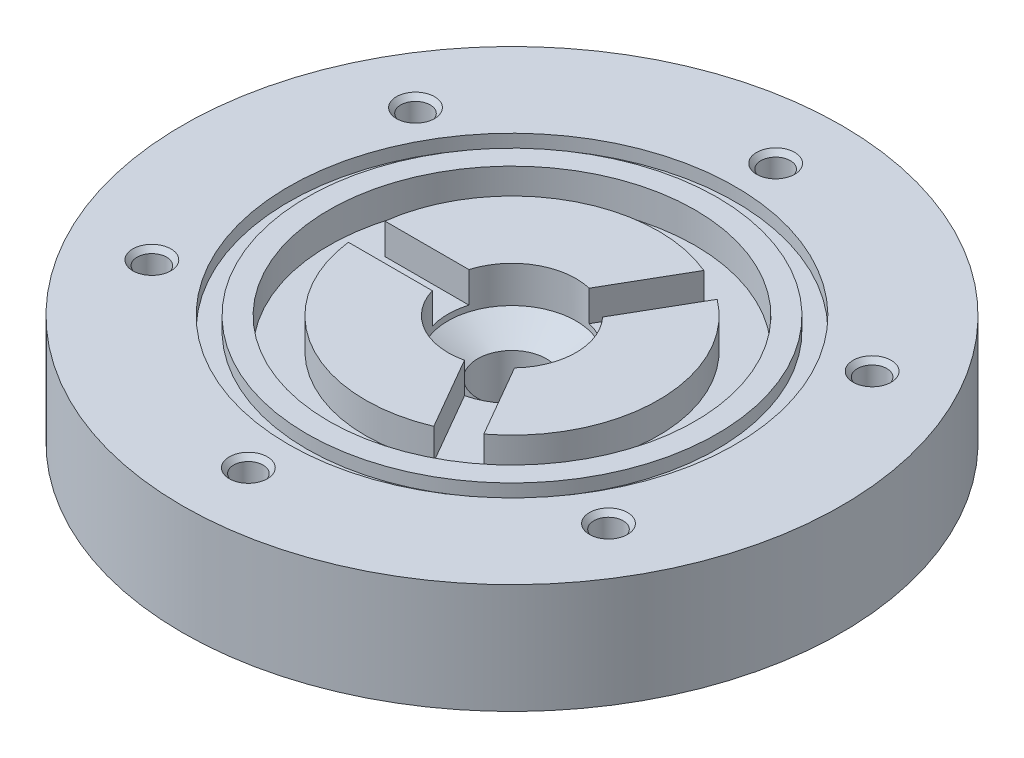
SolidWorks part; units mm, degrees
ref_plane "Front Plane" through (0, 0, 0) normal (0, 0, 1) x (1, 0, 0)
ref_plane "Top Plane" through (0, 0, 0) normal (0, 1, 0) x (1, 0, 0)
ref_plane "Right Plane" through (0, 0, 0) normal (1, 0, 0) x (0, 0, -1)
sketch "Sketch1" plane through (0, 0, 0) normal (0, 1, 0) x (1, 0, 0)
  circle A0 centre (0, 0) radius 57.15
  point P0 (0, 0)
  dimension "D3" = 114.3
extrude "Boss-Extrude1" add sketch "Sketch1" along normal blind 19.05
hole_wizard "7/8 (0.875) Diameter Hole1" positions "Sketch2" profile "Sketch3" hole size "7/8" standard "ANSI Inch"
sketch "Sketch2" plane through (0, 19.05, 0) normal (0, 1, 0) x (1, 0, 0)
  point P0 (0, 0)
sketch "Sketch3" plane through (0, 19.05, 0) normal (1, 0, 0) x (0, 0, 1)
  line L0 (0, 0) -> (0, 13.0271)
  line L1 (0, 13.0271) -> (11.1125, 6.35)
  line L2 (11.1125, 6.35) -> (11.1125, 0)
  line L5 (11.1125, 0) -> (0, 0)
  line L10 (0, 13.0271) -> (-11.1125, 6.35) construction
  line L11 (0, -6.35) -> (0, 107.95) construction
  dimension "Hole Dia." = 22.225
  dimension "Hole Depth" = 6.35
  dimension "Drill Angle" = 118
sketch "Sketch4" plane through (0, 19.05, 0) normal (0, 1, 0) x (1, 0, 0)
  circle A0 centre (0, 0) radius 5.9531
  dimension "D1" = 11.9062
extrude "Cut-Extrude1" cut sketch "Sketch4" against normal through all both and the other way through all
sketch "Sketch5" plane through (0, 19.05, 0) normal (0, 1, 0) x (1, 0, 0)
  line L0 (0, 0) -> (-57.15, 0) construction
  line L2 (-10.6493, 3.175) -> (-25.2008, 3.175)
  line L3 (-10.6493, -3.175) -> (-25.2008, -3.175)
  line L4 (0, -3.175) -> (-63.5, -3.175) construction
  line L5 (0, 3.175) -> (-63.5, 3.175) construction
  line L6 (2.575, 10.81) -> (9.8508, 23.412)
  line L7 (8.0743, 7.635) -> (15.35, 20.237)
  line L8 (0, 0) -> (28.575, 49.4934) construction
  line L9 (8.0743, -7.635) -> (15.35, -20.237)
  line L10 (2.575, -10.81) -> (9.8508, -23.412)
  line L11 (0, 0) -> (28.575, -49.4934) construction
  line L12 (0, 0) -> (-63.5, 0) construction
  arc A0 (15.35, -20.237) -> (15.35, 20.237) centre (0, 0) ccw
  circle A1 centre (0, 0) radius 31.75
  arc A2 (2.575, -10.81) -> (8.0743, -7.635) centre (0, 0) ccw
  arc A3 (-10.6493, 3.175) -> (-10.6493, -3.175) centre (0, 0) ccw
  arc A4 (8.0743, 7.635) -> (2.575, 10.81) centre (0, 0) ccw
  arc A5 (-25.2008, -3.175) -> (9.8508, -23.412) centre (0, 0) ccw
  arc A6 (9.8508, 23.412) -> (-25.2008, 3.175) centre (0, 0) ccw
  circle A8 centre (0, 0) radius 57.15 construction
  point P29 (0, 0)
  dimension "D1" = 50.8
  dimension "D2" = 63.5
  dimension "D5" = 22.225
  dimension "D3" = 3.175
  dimension "D4" = 3.175
  dimension "D6" = 3
ref_axis "Axis1" through (0, 12.7, 0) along (0, 1, 0)
extrude "Cut-Extrude3" cut sketch "Sketch5" against normal blind 5.334
sketch "Sketch6" plane through (0, 19.05, 0) normal (0, 1, 0) x (1, 0, 0)
  circle A0 centre (0, 0) radius 53.975 construction
  dimension "D1" = 107.95
sketch "Sketch7" plane through (0, 19.05, 0) normal (0, 1, 0) x (1, 0, 0)
  circle A0 centre (0, 0) radius 35.56
  circle A1 centre (0, 0) radius 38.735
  dimension "D1" = 71.12
  dimension "D2" = 77.47
extrude "Cut-Extrude5" cut sketch "Sketch7" against normal blind 2.286
hole_wizard "1/4-20 Tapped Hole1" positions "Sketch8" profile "Sketch9" tap size "1/4-20" standard "ANSI Inch"
sketch "Sketch8" plane through (0, 19.05, 0) normal (0, 1, 0) x (1, 0, 0)
  point P0 (0, 45.72)
  dimension "D1" = 45.72
sketch "Sketch9" plane through (0, 19.05, -45.72) normal (1, 0, 0) x (0, 0, 1)
  line L0 (0, 0) -> (0, 15.5038)
  line L1 (0, 15.5038) -> (2.5527, 13.97)
  line L2 (2.5527, 13.97) -> (2.5527, 0.862)
  line L3 (2.5527, 0.862) -> (3.302, 0)
  line L5 (3.302, 0) -> (0, 0)
  line L6 (-2.5527, 0.862) -> (-3.302, 0) construction
  line L10 (0, 15.5038) -> (-2.5527, 13.97) construction
  line L11 (0, -6.35) -> (0, 107.95) construction
  dimension "Tap Drill Dia." = 5.1054
  dimension "Tap Drill Depth" = 13.97
  dimension "Near C'Sink Dia." = 6.604
  dimension "Near C'Sink Angle" = 82
  dimension "Drill Angle" = 118
cosmetic thread "Hole Thread1" parameters "D1"=11.43, "D2"=6.35
pattern_circular "CirPattern1" count 6 over 360 about axis through (0, 12.7, 0) along (0, 1, 0) of "1/4-20 Tapped Hole1"
